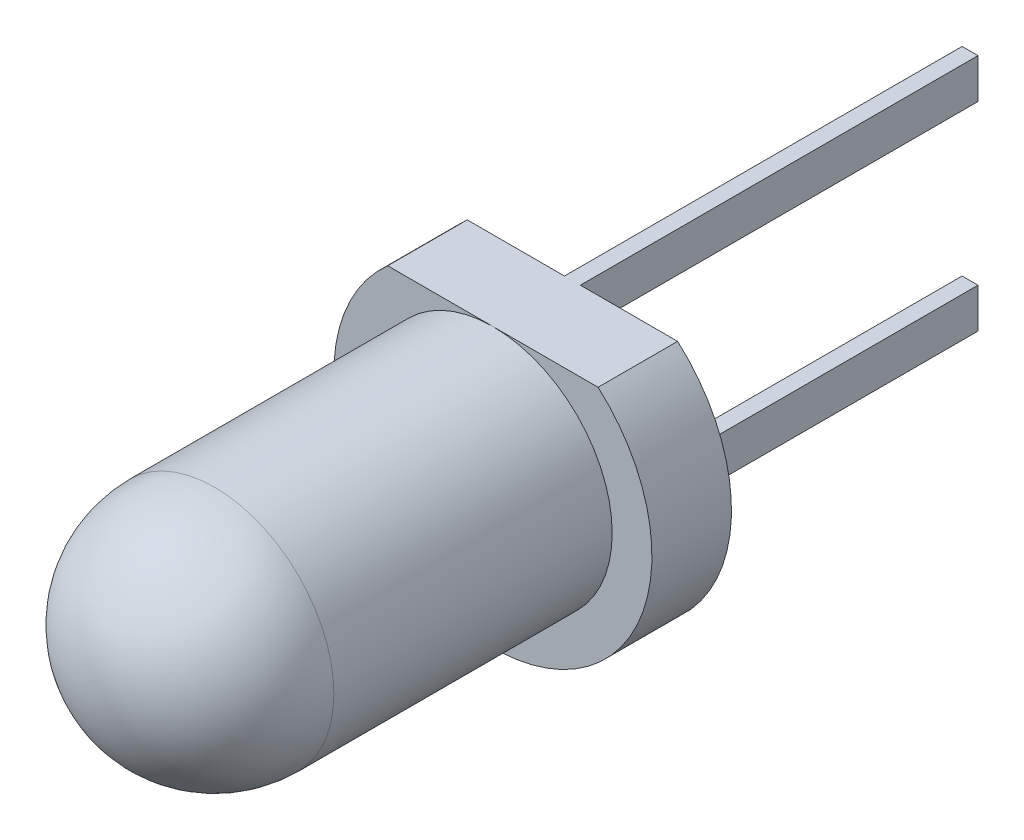
SolidWorks part; units mm, degrees
material "PW110:Mi:0:51:Ar:0:-1:C1:1:2:3:Re:5:Di:13:Tr:19:"
ref_plane "Front" through (0, 0, 0) normal (0, 0, 1) x (1, 0, 0)
ref_plane "Top" through (0, 0, 0) normal (0, 1, 0) x (1, 0, 0)
ref_plane "Right" through (0, 0, 0) normal (1, 0, 0) x (0, 0, -1)
sketch "Sketch1" plane through (0, 0, 0) normal (0, 0, 1) x (1, 0, 0)
  circle A0 centre (0, 0) radius 1.5
  dimension "D1" = 3
extrude "Base-Extrude" add sketch "Sketch1" along normal blind 3.5
dome "Dome1" faces to dome 1 distance 1.5 reverse direction no elliptical dome no face at (1.5, 0, 3.5) parameters "D1"=1.5
sketch "Sketch2" plane through (0, 0, 0) normal (0, 0, -1) x (-1, 0, 0)
  circle A0 centre (0, 0) radius 2
  dimension "D1" = 4
extrude "Boss-Extrude1" add sketch "Sketch2" along normal blind 1
sketch "Sketch3" plane through (0, 0, -1) normal (0, 0, -1) x (-1, 0, 0)
  line L0 (-0.5476, 0) -> (0.6044, 0) construction
  line L1 (-0.1, 1.5) -> (0.1, 1.5)
  line L2 (-0.1, 1.5) -> (-0.1, 1)
  line L3 (-0.1, 1) -> (0.1, 1)
  line L4 (0.1, 1.5) -> (0.1, 1)
  line L5 (0.1, -1.5) -> (0.1, -1)
  line L6 (-0.1, -1) -> (0.1, -1)
  line L7 (-0.1, -1.5) -> (-0.1, -1)
  line L8 (-0.1, -1.5) -> (0.1, -1.5)
  dimension "D1" = 0.5
  dimension "D2" = 0.2
  dimension "D3" = 1.5
  dimension "D4" = 0.1
extrude "Boss-Extrude2" add sketch "Sketch3" along normal blind 5
ref_plane "Plane1" through (-0.1, 1, -6) normal (-1, 0, 0) x (0, 0, 1)
sketch "Sketch5" plane through (0, 0, -1) normal (0, 0, -1) x (-1, 0, 0)
  line L0 (-1.3229, 1.5) -> (1.3229, 1.5)
  circle A0 centre (0, 0) radius 2 construction
extrude "Cut-Extrude1" cut sketch "Sketch5" against normal through all and the other way through all
